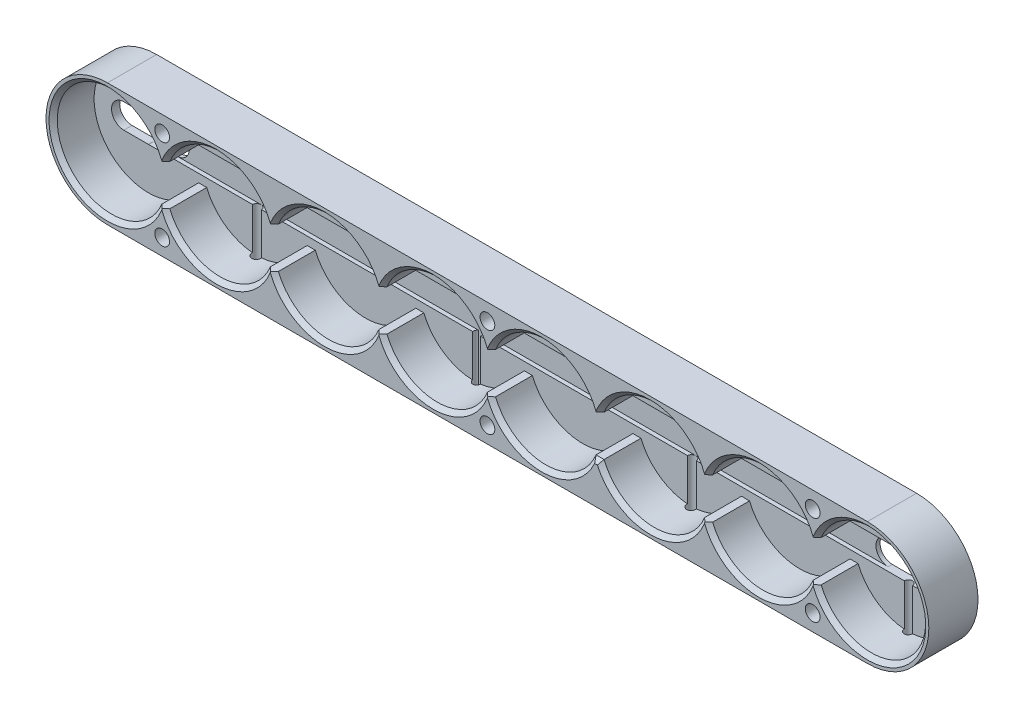
SolidWorks part; units mm, degrees
ref_plane "Front Plane" through (0, 0, 0) normal (0, 0, 1) x (1, 0, 0)
ref_plane "Top Plane" through (0, 0, 0) normal (0, 1, 0) x (1, 0, 0)
ref_plane "Right Plane" through (0, 0, 0) normal (1, 0, 0) x (0, 0, -1)
sketch "Sketch1" plane through (0, 0, 0) normal (0, 0, 1) x (1, 0, 0)
  line L0 (0, 0) -> (185.5, 0)
  line L1 (0, 15) -> (185.5, 15)
  line L2 (0, -15) -> (185.5, -15)
  line L3 (0, 5) -> (186.9, 5)
  line L4 (0, -5) -> (186.9, -5)
  circle A0 centre (0, 0) radius 13.25
  circle A1 centre (26.5, 0) radius 13.25
  circle A2 centre (53, 0) radius 13.25
  circle A3 centre (79.5, 0) radius 13.25
  circle A4 centre (106, 0) radius 13.25
  circle A5 centre (132.5, 0) radius 13.25
  circle A6 centre (159, 0) radius 13.25
  circle A7 centre (185.5, 0) radius 13.25
  arc A8 (0, 15) -> (0, -15) centre (0, 0) ccw
  arc A9 (185.5, -15) -> (185.5, 15) centre (185.5, 0) ccw
  dimension "D1" = 8
  dimension "D2" = 5
  dimension "D4" = 26.5
  dimension "D5" = 26.5
  dimension "D3" = 5
extrude "Boss-Extrude1" add sketch "Sketch1" along normal blind 10 contours L2 A9 L1 A8 A7 L4 A6 A5 A4 A3 A2 A1 A0 L3
sketch "Sketch2" plane through (0, 0, 0) normal (0, 0, -1) x (-1, 0, 0)
  line L0 (0, -15) -> (-185.5, -15) construction
  line L1 (0, 15) -> (-185.5, 15) construction
  line L2 (0, -15) -> (-185.5, -15)
  line L3 (0, 15) -> (-185.5, 15)
  arc A0 (-185.5, 15) -> (-185.5, -15) centre (-185.5, 0) ccw construction
  arc A1 (0, -15) -> (0, 15) centre (0, 0) ccw construction
  arc A2 (-185.5, 15) -> (-185.5, -15) centre (-185.5, 0) ccw
  arc A3 (0, -15) -> (0, 15) centre (0, 0) ccw
extrude "Boss-Extrude2" add sketch "Sketch2" along normal blind 2
chamfer "Chamfer4" distance 1 angle 45 15 edges at (-13.25, 0, 10) (26.5, 13.25, 10) (26.5, -13.25, 10) (53, 13.25, 10) (53, -13.25, 10) (79.5, 13.25, 10) (79.5, -13.25, 10) (106, 13.25, 10) (132.5, 13.25, 10) (159, 13.25, 10) (159, -13.25, 10) (198.75, 0, 10) (106, -13.25, 10) (132.5, -13.25, 10) (119.25, -5, 10)
sketch "Sketch4" plane through (0, 0, -2) normal (0, 0, -1) x (-1, 0, 0)
  line L0 (-186.9, -3) -> (-180.9, -3)
  line L1 (-186.9, 3) -> (-180.9, 3)
  line L2 (-192.9, -3) -> (-186.9, -3)
  line L3 (-192.9, 3) -> (-186.9, 3)
  line L5 (-92.75, -18.8272) -> (-92.75, 15) construction
  line L6 (0, 15) -> (-185.5, 15) construction
  line L7 (7.4, 3) -> (1.4, 3)
  line L8 (7.4, -3) -> (1.4, -3)
  line L9 (1.4, 3) -> (-4.6, 3)
  line L10 (1.4, -3) -> (-4.6, -3)
  arc A1 (-180.9, -3) -> (-180.9, 3) centre (-180.9, 0) ccw
  arc A2 (-192.9, 3) -> (-192.9, -3) centre (-192.9, 0) ccw
  arc A3 (7.4, 3) -> (7.4, -3) centre (7.4, 0) cw
  arc A4 (-4.6, -3) -> (-4.6, 3) centre (-4.6, 0) cw
sketch "Sketch5" plane through (0, 0, 10) normal (0, 0, 1) x (1, 0, 0)
  line L0 (0, 0) -> (185.5, 0) construction
  circle A0 centre (13.35, 11) radius 1.8
  circle A1 centre (92.75, 11) radius 1.8
  circle A2 centre (172.15, 11) radius 1.8
  circle A3 centre (92.75, -11) radius 1.8
  circle A4 centre (172.15, -11) radius 1.8
  circle A5 centre (13.35, -11) radius 1.8
  point P4 (13.25, 5.244)
  dimension "D1" = 3.6
  dimension "D5" = 79.4
  dimension "12" = 11
  dimension "D4" = 79.4
  dimension "D2" = 3
  dimension "D3" = 2
extrude "Cut-Extrude2" cut sketch "Sketch5" against normal blind 12
sketch "Sketch6" plane through (0, 0, -2) normal (0, 0, -1) x (-1, 0, 0)
  circle A0 centre (-13.35, 11) radius 2.9
  circle A1 centre (-92.75, 11) radius 2.9
  circle A2 centre (-172.15, 11) radius 2.9
  circle A3 centre (-92.75, -11) radius 2.9
  circle A4 centre (-172.15, -11) radius 2.9
  circle A5 centre (-13.35, -11) radius 2.9
  dimension "D1" = 3
  dimension "D3" = 79.4
  dimension "D2" = 2
extrude "Cut-Extrude3" cut sketch "Sketch6" against normal blind 4.5
chamfer "Chamfer5" distance 1.1 angle 45 6 edges at (10.45, -11, 2.5) (169.25, 11, 2.5) (169.25, -11, 2.5) (89.85, -11, 2.5) (89.85, 11, 2.5) (10.45, 11, 2.5)
sketch "Sketch7" plane through (0, 0, -2) normal (0, 0, -1) x (-1, 0, 0)
  line L0 (0, 0) -> (0, 4.1725) construction
sketch "Sketch9" plane through (0, 0, 0) normal (0, 0, 1) x (1, 0, 0)
  line L4 (185.5, 3) -> (0.0868, 3)
  line L5 (0.0868, -3) -> (185.5, -3)
  arc A0 (0.0868, 3) -> (0.0868, -3) centre (0, 0) ccw
  arc A1 (185.5, -3) -> (185.5, 3) centre (185.5, 0) ccw
extrude "Cut-Extrude6" cut sketch "Sketch9" against normal blind 1
sketch "Sketch10" plane through (0, -15, 0) normal (0, -1, 0) x (1, 0, 0)
  line L0 (39.75, 10) -> (13.25, 10) construction
  line L1 (39.75, 10) -> (13.25, 10)
  line L2 (185.5, 10) -> (185.5, -2) construction
  line L4 (0.0868, -1) -> (185.5, -1) construction
  line L6 (145.75, 10) -> (119.5747, 10) construction
  line L7 (92.75, 10) -> (66.25, 10) construction
  line L8 (92.75, 10) -> (66.25, 10)
  line L9 (145.75, 10) -> (119.5747, 10)
  line L10 (0.0868, -1) -> (185.5, -1)
  circle A4 centre (132.6624, 0.1284) radius 1.1284
  circle A6 centre (26.5, 0.1284) radius 1.1284
  circle A7 centre (79.5812, 0.1284) radius 1.1284 [skipped]
  circle A8 centre (80.1003, -0.1277) radius 1
  circle A9 centre (185.5, 0) radius 1
  point P6 (132.6624, 0.1284)
  point P13 (79.5, 10)
  point P20 (132.6624, 10)
  point P22 (26.5, 10)
  line M4 (185.5, -2) -> (185.5, 10)
  dimension "D1" = 3
extrude "Cut-Extrude9" cut sketch "Sketch10" against normal blind 13 contours A6 | A8 | A4 | A9 M4
sketch "Sketch11" plane through (0, 0, -1) normal (0, 0, 1) x (1, 0, 0)
  line L0 (-6, 3) -> (6, 3)
  line L1 (-6, -3) -> (6, -3)
  line L2 (92.7934, 3) -> (92.7934, -4.4631) construction
  line L3 (185.5, 3) -> (0.0868, 3) construction
  line L4 (191.5868, -3) -> (179.5868, -3)
  line L5 (191.5868, 3) -> (179.5868, 3)
  arc A0 (-6, 3) -> (-6, -3) centre (-6, 0) ccw
  arc A1 (6, -3) -> (6, 3) centre (6, 0) ccw
  arc A2 (179.5868, -3) -> (179.5868, 3) centre (179.5868, 0) cw
  arc A3 (191.5868, 3) -> (191.5868, -3) centre (191.5868, 0) cw
  dimension "D1" = 6
  dimension "D2" = 6
extrude "Cut-Extrude10" cut sketch "Sketch11" against normal blind 10 and the other way blind 10
